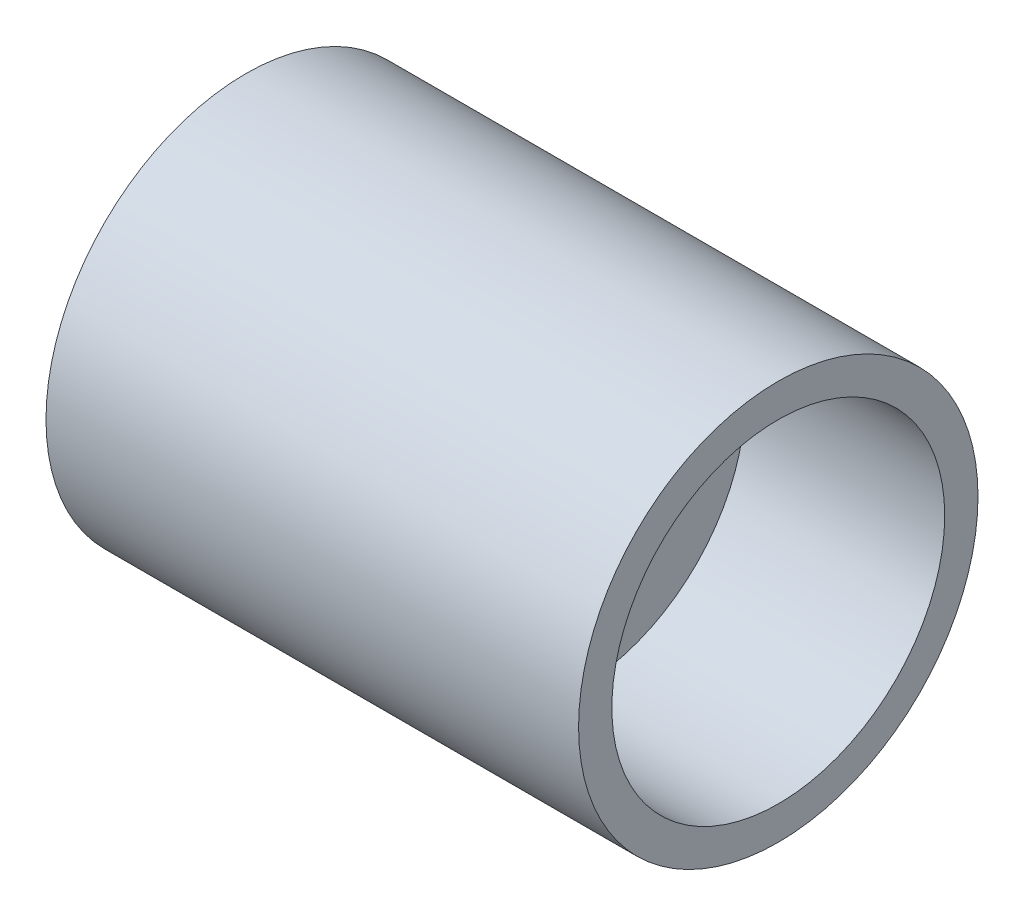
SolidWorks part; units mm, degrees
ref_plane "Front Plane" through (0, 0, 0) normal (0, 0, 1) x (1, 0, 0)
ref_plane "Top Plane" through (0, 0, 0) normal (0, 1, 0) x (1, 0, 0)
ref_plane "Right Plane" through (0, 0, 0) normal (1, 0, 0) x (0, 0, -1)
sketch "Sketch1" plane through (0, 0, 0) normal (1, 0, 0) x (0, 0, -1)
  circle A0 centre (0, 0) radius 3
  dimension "D1" = 6
extrude "Boss-Extrude1" add sketch "Sketch1" along normal blind 8
sketch "Sketch2" plane through (8, 0, 0) normal (1, 0, 0) x (0, 0, -1)
  circle A0 centre (0, 0) radius 2.5
  dimension "D1" = 5
extrude "Cut-Extrude1" cut sketch "Sketch2" against normal blind 3
sketch "Sketch3" plane through (0, 0, 0) normal (-1, 0, 0) x (0, 0, 1)
  circle A0 centre (0, 0) radius 2.5
  dimension "D1" = 5
extrude "Cut-Extrude2" cut sketch "Sketch3" against normal blind 2
